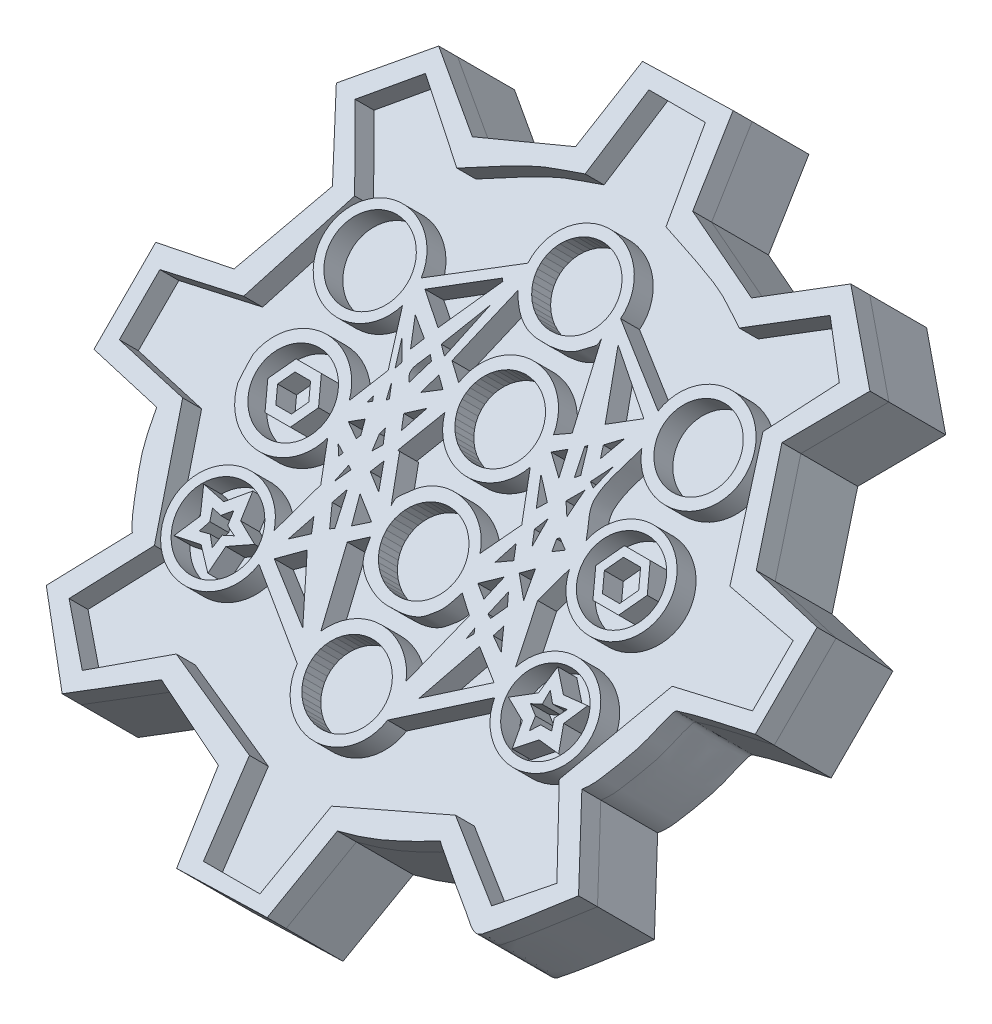
SolidWorks part; units mm, degrees
ref_plane "Front Plane" through (0, 0, 0) normal (0, 0, 1) x (1, 0, 0)
ref_plane "Top Plane" through (0, 0, 0) normal (0, 1, 0) x (1, 0, 0)
ref_plane "Right Plane" through (0, 0, 0) normal (1, 0, 0) x (0, 0, -1)
ref_plane "Plane2" through (0, -6.35, 0) normal (0, 1, 0) x (1, 0, 0)
sketch "Sketch2" plane through (0, -6.35, 0) normal (0, 1, 0) x (1, 0, 0)
  circle A0 centre (0, 0) radius 6.0325
  dimension "D1" = 12.065
ref_axis "Axis1" through (-6.2865, 0, 0) along (1, 0, 0)
ref_plane "Plane1" through (0, 0, 0) normal (0, 0.7071, 0.7071) x (1, 0, 0)
sketch "Sketch3" plane through (0, 0, 0) normal (0, 0.7071, 0.7071) x (1, 0, 0)
  line L0 (0, 0) -> (-25.4, 0) construction
  line L1 (-6.2865, 0) -> (6.2865, 0) construction
  line L2 (-25.4, -38.1) -> (-25.4, 38.1) construction
  circle A0 centre (0, 0) radius 12.7
  point P13 (-25.4, 0)
  point P15 (-20.32, 7.62)
  point P16 (-20.32, -7.62)
  point P17 (-20.32, -22.86)
  dimension "D1" = 25.4
  dimension "D4" = 25.4
  dimension "D5" = 76.2
extrude "Boss-Extrude1" add sketch "Sketch3" along normal blind 4.7625
extrude "Boss-Extrude2" add sketch "Sketch2" along normal up to surface and the other way blind 3.175 up to face at (0, -8.9803, 8.9803)
sketch "Sketch5" plane through (0, 3.3676, 3.3676) normal (0, 0.7071, 0.7071) x (1, 0, 0)
  line L0 (2.1384, 9.1764) -> (2.1514, 9.4647)
  line L1 (2.1514, 9.4647) -> (2.125, 9.7523)
  line L2 (2.125, 9.7523) -> (2.0598, 10.0341)
  line L3 (2.0598, 10.0341) -> (1.9568, 10.3051)
  line L4 (1.9568, 10.3051) -> (1.818, 10.5603)
  line L5 (1.818, 10.5603) -> (1.6457, 10.7953)
  line L6 (1.6457, 10.7953) -> (1.4431, 11.0059)
  line L7 (1.4431, 11.0059) -> (1.2138, 11.1882)
  line L8 (1.2138, 11.1882) -> (0.9619, 11.3391)
  line L9 (0.9619, 11.3391) -> (0.6918, 11.4559)
  line L10 (0.6918, 11.4559) -> (0.4085, 11.5365)
  line L11 (0.4085, 11.5365) -> (0.1168, 11.5794)
  line L12 (0.1168, 11.5794) -> (-0.1778, 11.5838)
  line L13 (-0.1778, 11.5838) -> (-0.4703, 11.5498)
  line L14 (-0.4703, 11.5498) -> (-0.7553, 11.4779)
  line L15 (-0.7553, 11.4779) -> (-1.0279, 11.3693)
  line L16 (-1.0279, 11.3693) -> (-1.283, 11.2261)
  line L17 (-1.283, 11.2261) -> (-1.5162, 11.0507)
  line L18 (-1.5162, 11.0507) -> (-1.7233, 10.8463)
  line L19 (-1.7233, 10.8463) -> (-1.9007, 10.6166)
  line L20 (-1.9007, 10.6166) -> (-2.045, 10.3657)
  line L21 (-2.045, 10.3657) -> (-2.1539, 10.098)
  line L22 (-2.1539, 10.098) -> (-2.2253, 9.8183)
  line L23 (-2.2253, 9.8183) -> (-2.2579, 9.5315)
  line L24 (-2.2579, 9.5315) -> (-2.2512, 9.243)
  line L25 (-2.2512, 9.243) -> (-2.2053, 8.9576)
  line L26 (-2.2053, 8.9576) -> (-2.121, 8.6806)
  line L27 (-2.121, 8.6806) -> (-1.9998, 8.417)
  line L28 (-1.9998, 8.417) -> (-1.8439, 8.1713)
  line L29 (-1.8439, 8.1713) -> (-1.6561, 7.948)
  line L30 (-1.6561, 7.948) -> (-1.4396, 7.7511)
  line L31 (-1.4396, 7.7511) -> (-1.1985, 7.5841)
  line L32 (-1.1985, 7.5841) -> (-0.9369, 7.45)
  line L33 (-0.9369, 7.45) -> (-0.6596, 7.3511)
  line L34 (-0.6596, 7.3511) -> (-0.3714, 7.2892)
  line L35 (-0.3714, 7.2892) -> (-0.0776, 7.2655)
  line L36 (-0.0776, 7.2655) -> (0.2166, 7.2803)
  line L37 (0.2166, 7.2803) -> (0.506, 7.3334)
  line L38 (0.506, 7.3334) -> (0.7854, 7.4239)
  line L39 (0.7854, 7.4239) -> (1.0498, 7.55)
  line L40 (1.0498, 7.55) -> (1.2946, 7.7097)
  line L41 (1.2946, 7.7097) -> (1.5152, 7.9)
  line L42 (1.5152, 7.9) -> (1.7079, 8.1175)
  line L43 (1.7079, 8.1175) -> (1.8691, 8.3584)
  line L44 (1.8691, 8.3584) -> (1.996, 8.6183)
  line L45 (1.996, 8.6183) -> (2.0863, 8.8926)
  line L46 (2.0863, 8.8926) -> (2.1384, 9.1764)
  line L47 (2.1553, 2.9225) -> (2.146, 3.2114)
  line L48 (2.146, 3.2114) -> (2.0975, 3.4967)
  line L49 (2.0975, 3.4967) -> (2.0105, 3.7731)
  line L50 (2.0105, 3.7731) -> (1.8868, 4.0357)
  line L51 (1.8868, 4.0357) -> (1.7284, 4.2799)
  line L52 (1.7284, 4.2799) -> (1.5383, 4.5013)
  line L53 (1.5383, 4.5013) -> (1.3198, 4.696)
  line L54 (1.3198, 4.696) -> (1.0768, 4.8604)
  line L55 (1.0768, 4.8604) -> (0.8136, 4.9916)
  line L56 (0.8136, 4.9916) -> (0.535, 5.0874)
  line L57 (0.535, 5.0874) -> (0.2459, 5.1459)
  line L58 (0.2459, 5.1459) -> (-0.0486, 5.1662)
  line L59 (-0.0486, 5.1662) -> (-0.3431, 5.1478)
  line L60 (-0.3431, 5.1478) -> (-0.6324, 5.0912)
  line L61 (-0.6324, 5.0912) -> (-0.9114, 4.9973)
  line L62 (-0.9114, 4.9973) -> (-1.1751, 4.8677)
  line L63 (-1.1751, 4.8677) -> (-1.4187, 4.7049)
  line L64 (-1.4187, 4.7049) -> (-1.638, 4.5117)
  line L65 (-1.638, 4.5117) -> (-1.8289, 4.2915)
  line L66 (-1.8289, 4.2915) -> (-1.9882, 4.0484)
  line L67 (-1.9882, 4.0484) -> (-2.1129, 3.7865)
  line L68 (-2.1129, 3.7865) -> (-2.2009, 3.5107)
  line L69 (-2.2009, 3.5107) -> (-2.2505, 3.2258)
  line L70 (-2.2505, 3.2258) -> (-2.2609, 2.9369)
  line L71 (-2.2609, 2.9369) -> (-2.2319, 2.6491)
  line L72 (-2.2319, 2.6491) -> (-2.164, 2.3677)
  line L73 (-2.164, 2.3677) -> (-2.0585, 2.0975)
  line L74 (-2.0585, 2.0975) -> (-1.9171, 1.8436)
  line L75 (-1.9171, 1.8436) -> (-1.7425, 1.6102)
  line L76 (-1.7425, 1.6102) -> (-1.5377, 1.4017)
  line L77 (-1.5377, 1.4017) -> (-1.3064, 1.2218)
  line L78 (-1.3064, 1.2218) -> (-1.0527, 1.0737)
  line L79 (-1.0527, 1.0737) -> (-0.7812, 0.9599)
  line L80 (-0.7812, 0.9599) -> (-0.4967, 0.8826)
  line L81 (-0.4967, 0.8826) -> (-0.2043, 0.8431)
  line L82 (-0.2043, 0.8431) -> (0.0908, 0.8421)
  line L83 (0.0908, 0.8421) -> (0.3834, 0.8797)
  line L84 (0.3834, 0.8797) -> (0.6682, 0.9552)
  line L85 (0.6682, 0.9552) -> (0.9401, 1.0671)
  line L86 (0.9401, 1.0671) -> (1.1944, 1.2137)
  line L87 (1.1944, 1.2137) -> (1.4263, 1.3921)
  line L88 (1.4263, 1.3921) -> (1.6319, 1.5992)
  line L89 (1.6319, 1.5992) -> (1.8074, 1.8314)
  line L90 (1.8074, 1.8314) -> (1.9497, 2.0845)
  line L91 (1.9497, 2.0845) -> (2.0563, 2.3539)
  line L92 (2.0563, 2.3539) -> (2.1252, 2.6349)
  line L93 (2.1252, 2.6349) -> (2.1553, 2.9225)
  line L94 (2.1447, -3.5357) -> (2.1432, -3.2468)
  line L95 (2.1432, -3.2468) -> (2.1025, -2.9605)
  line L96 (2.1025, -2.9605) -> (2.0232, -2.682)
  line L97 (2.0232, -2.682) -> (1.9066, -2.4162)
  line L98 (1.9066, -2.4162) -> (1.755, -2.1679)
  line L99 (1.755, -2.1679) -> (1.571, -1.9415)
  line L100 (1.571, -1.9415) -> (1.3579, -1.7411)
  line L101 (1.3579, -1.7411) -> (1.1195, -1.5702)
  line L102 (1.1195, -1.5702) -> (0.8601, -1.4319)
  line L103 (0.8601, -1.4319) -> (0.5842, -1.3286)
  line L104 (0.5842, -1.3286) -> (0.2968, -1.2622)
  line L105 (0.2968, -1.2622) -> (0.003, -1.2339)
  line L106 (0.003, -1.2339) -> (-0.2918, -1.2442)
  line L107 (-0.2918, -1.2442) -> (-0.5826, -1.2929)
  line L108 (-0.5826, -1.2929) -> (-0.864, -1.3791)
  line L109 (-0.864, -1.3791) -> (-1.1311, -1.5013)
  line L110 (-1.1311, -1.5013) -> (-1.379, -1.6573)
  line L111 (-1.379, -1.6573) -> (-1.6034, -1.8443)
  line L112 (-1.6034, -1.8443) -> (-1.8003, -2.059)
  line L113 (-1.8003, -2.059) -> (-1.9662, -2.2976)
  line L114 (-1.9662, -2.2976) -> (-2.098, -2.5558)
  line L115 (-2.098, -2.5558) -> (-2.1934, -2.8289)
  line L116 (-2.1934, -2.8289) -> (-2.2508, -3.1122)
  line L117 (-2.2508, -3.1122) -> (-2.2691, -3.4006)
  line L118 (-2.2691, -3.4006) -> (-2.248, -3.6888)
  line L119 (-2.248, -3.6888) -> (-2.1878, -3.9719)
  line L120 (-2.1878, -3.9719) -> (-2.0896, -4.2446)
  line L121 (-2.0896, -4.2446) -> (-1.9553, -4.5022)
  line L122 (-1.9553, -4.5022) -> (-1.7871, -4.7401)
  line L123 (-1.7871, -4.7401) -> (-1.5881, -4.954)
  line L124 (-1.5881, -4.954) -> (-1.3618, -5.1401)
  line L125 (-1.3618, -5.1401) -> (-1.1123, -5.295)
  line L126 (-1.1123, -5.295) -> (-0.8441, -5.4161)
  line L127 (-0.8441, -5.4161) -> (-0.5618, -5.5011)
  line L128 (-0.5618, -5.5011) -> (-0.2706, -5.5485)
  line L129 (-0.2706, -5.5485) -> (0.0244, -5.5576)
  line L130 (0.0244, -5.5576) -> (0.3179, -5.528)
  line L131 (0.3179, -5.528) -> (0.6046, -5.4604)
  line L132 (0.6046, -5.4604) -> (0.8794, -5.356)
  line L133 (0.8794, -5.356) -> (1.1375, -5.2166)
  line L134 (1.1375, -5.2166) -> (1.3742, -5.0447)
  line L135 (1.3742, -5.0447) -> (1.5854, -4.8434)
  line L136 (1.5854, -4.8434) -> (1.7671, -4.6162)
  line L137 (1.7671, -4.6162) -> (1.9163, -4.3673)
  line L138 (1.9163, -4.3673) -> (2.0302, -4.101)
  line L139 (2.0302, -4.101) -> (2.1067, -3.8222)
  line L140 (2.1067, -3.8222) -> (2.1447, -3.5357)
  line L141 (2.1098, -10.2575) -> (2.1477, -9.9761)
  line L142 (2.1477, -9.9761) -> (2.1479, -9.692)
  line L143 (2.1479, -9.692) -> (2.1103, -9.41)
  line L144 (2.1103, -9.41) -> (2.0357, -9.135)
  line L145 (2.0357, -9.135) -> (1.9252, -8.8716)
  line L146 (1.9252, -8.8716) -> (1.7807, -8.6245)
  line L147 (1.7807, -8.6245) -> (1.6048, -8.3977)
  line L148 (1.6048, -8.3977) -> (1.4005, -8.1951)
  line L149 (1.4005, -8.1951) -> (1.1711, -8.0204)
  line L150 (1.1711, -8.0204) -> (0.9208, -7.8763)
  line L151 (0.9208, -7.8763) -> (0.6537, -7.7655)
  line L152 (0.6537, -7.7655) -> (0.3744, -7.6897)
  line L153 (0.3744, -7.6897) -> (0.0877, -7.6504)
  line L154 (0.0877, -7.6504) -> (-0.2014, -7.6481)
  line L155 (-0.2014, -7.6481) -> (-0.4882, -7.6829)
  line L156 (-0.4882, -7.6829) -> (-0.7675, -7.7542)
  line L157 (-0.7675, -7.7542) -> (-1.0348, -7.8608)
  line L158 (-1.0348, -7.8608) -> (-1.2853, -8.0008)
  line L159 (-1.2853, -8.0008) -> (-1.5148, -8.172)
  line L160 (-1.5148, -8.172) -> (-1.7194, -8.3712)
  line L161 (-1.7194, -8.3712) -> (-1.8956, -8.5952)
  line L162 (-1.8956, -8.5952) -> (-2.0403, -8.8401)
  line L163 (-2.0403, -8.8401) -> (-2.1511, -9.1017)
  line L164 (-2.1511, -9.1017) -> (-2.2262, -9.3755)
  line L165 (-2.2262, -9.3755) -> (-2.2641, -9.6569)
  line L166 (-2.2641, -9.6569) -> (-2.2642, -9.941)
  line L167 (-2.2642, -9.941) -> (-2.2267, -10.223)
  line L168 (-2.2267, -10.223) -> (-2.152, -10.498)
  line L169 (-2.152, -10.498) -> (-2.0415, -10.7613)
  line L170 (-2.0415, -10.7613) -> (-1.897, -11.0085)
  line L171 (-1.897, -11.0085) -> (-1.7211, -11.2353)
  line L172 (-1.7211, -11.2353) -> (-1.5168, -11.4378)
  line L173 (-1.5168, -11.4378) -> (-1.2875, -11.6126)
  line L174 (-1.2875, -11.6126) -> (-1.0371, -11.7567)
  line L175 (-1.0371, -11.7567) -> (-0.77, -11.8675)
  line L176 (-0.77, -11.8675) -> (-0.4907, -11.9433)
  line L177 (-0.4907, -11.9433) -> (-0.2041, -11.9826)
  line L178 (-0.2041, -11.9826) -> (0.0851, -11.9849)
  line L179 (0.0851, -11.9849) -> (0.3718, -11.9501)
  line L180 (0.3718, -11.9501) -> (0.6512, -11.8788)
  line L181 (0.6512, -11.8788) -> (0.9184, -11.7722)
  line L182 (0.9184, -11.7722) -> (1.169, -11.6321)
  line L183 (1.169, -11.6321) -> (1.3985, -11.461)
  line L184 (1.3985, -11.461) -> (1.6031, -11.2618)
  line L185 (1.6031, -11.2618) -> (1.7793, -11.0378)
  line L186 (1.7793, -11.0378) -> (1.924, -10.7929)
  line L187 (1.924, -10.7929) -> (2.0348, -10.5313)
  line L188 (2.0348, -10.5313) -> (2.1098, -10.2575)
  line L189 (11.1815, -5.5544) -> (9.8248, -5.6673)
  line L190 (9.1225, -5.7799) -> (9.1225, -6.4565)
  line L191 (9.1225, -6.4565) -> (8.5826, -6.6798)
  line L192 (8.5826, -6.6798) -> (9.1225, -7.0175)
  line L193 (9.1225, -7.0175) -> (9.2346, -7.6897)
  line L194 (9.2346, -7.6897) -> (9.5792, -7.2361)
  line L195 (9.5792, -7.2361) -> (10.233, -7.2361)
  line L196 (10.233, -7.2361) -> (10.011, -6.6996)
  line L197 (10.011, -6.6996) -> (10.3747, -6.1182)
  line L198 (10.3747, -6.1182) -> (9.5792, -6.227)
  line L199 (9.5792, -6.227) -> (9.1225, -5.7799)
  line L200 (10.5709, -6.6996) -> (11.1815, -5.5544)
  line L201 (11.1233, -7.9115) -> (10.5709, -6.6996)
  line L202 (9.9061, -7.8107) -> (11.1233, -7.9115)
  line L203 (8.9329, -8.7049) -> (9.9061, -7.8107)
  line L204 (8.6664, -7.4675) -> (8.9329, -8.7049)
  line L205 (7.4397, -6.9096) -> (8.6664, -7.4675)
  line L206 (8.6664, -6.1182) -> (7.4397, -6.9096)
  line L207 (8.8526, -4.7674) -> (8.6664, -6.1182)
  line L208 (9.8248, -5.6673) -> (8.8526, -4.7674)
  line L209 (7.9446, -0.3005) -> (8.7074, -1.6217)
  line L210 (10.4872, -0.3005) -> (9.9787, 0.5803)
  line L211 (9.9787, 0.5803) -> (8.9617, 0.5803)
  line L212 (8.9617, 0.5803) -> (8.4532, -0.3005)
  line L213 (8.4532, -0.3005) -> (8.9617, -1.1812)
  line L214 (8.9617, -1.1812) -> (9.9787, -1.1812)
  line L215 (9.9787, -1.1812) -> (10.4872, -0.3005)
  line L216 (8.7074, 1.0207) -> (7.9446, -0.3005)
  line L217 (10.233, 1.0207) -> (8.7074, 1.0207)
  line L218 (10.9958, -0.3005) -> (10.233, 1.0207)
  line L219 (10.233, -1.6217) -> (10.9958, -0.3005)
  line L220 (8.7074, -1.6217) -> (10.233, -1.6217)
  line L221 (-11.4271, -0.3799) -> (-10.6764, -1.6802)
  line L222 (-9.0014, -0.3799) -> (-9.4635, 0.4205)
  line L223 (-9.4635, 0.4205) -> (-10.3877, 0.4205)
  line L224 (-10.3877, 0.4205) -> (-10.8498, -0.3799)
  line L225 (-10.8498, -0.3799) -> (-10.3877, -1.1803)
  line L226 (-10.3877, -1.1803) -> (-9.4635, -1.1803)
  line L227 (-9.4635, -1.1803) -> (-9.0014, -0.3799)
  line L228 (-10.6764, 0.9204) -> (-11.4271, -0.3799)
  line L229 (-9.1749, 0.9204) -> (-10.6764, 0.9204)
  line L230 (-8.4241, -0.3799) -> (-9.1749, 0.9204)
  line L231 (-9.1749, -1.6802) -> (-8.4241, -0.3799)
  line L232 (-10.6764, -1.6802) -> (-9.1749, -1.6802)
  line L233 (-9.9942, -7.2361) -> (-10.5615, -7.3583)
  line L234 (-11.5651, -5.5544) -> (-10.2232, -5.7799)
  line L235 (-10.2232, -5.7799) -> (-9.2055, -4.7798)
  line L236 (-9.2055, -4.7798) -> (-8.9824, -6.1183)
  line L237 (-8.9824, -6.1183) -> (-7.7542, -6.6768)
  line L238 (-7.7542, -6.6768) -> (-8.9824, -7.3583)
  line L239 (-8.9824, -7.3583) -> (-9.0939, -8.7049)
  line L240 (-9.0939, -8.7049) -> (-10.1253, -7.8107)
  line L241 (-10.1253, -7.8107) -> (-11.5651, -8.0507)
  line L242 (-11.5651, -8.0507) -> (-10.8942, -6.7924)
  line L243 (-10.8942, -6.7924) -> (-11.5651, -5.5544)
  line L244 (-9.5485, -7.6897) -> (-9.9942, -7.2361)
  line L245 (-9.4371, -7.0269) -> (-9.5485, -7.6897)
  line L246 (-8.8749, -6.7924) -> (-9.4371, -7.0269)
  line L247 (-9.4371, -6.5611) -> (-8.8749, -6.7924)
  line L248 (-9.5485, -5.8929) -> (-9.4371, -6.5611)
  line L249 (-10.0073, -6.3437) -> (-9.5485, -5.8929)
  line L250 (-10.5615, -6.2297) -> (-10.0073, -6.3437)
  line L251 (-10.3287, -6.7924) -> (-10.5615, -6.2297)
  line L252 (-10.5615, -7.3583) -> (-10.3287, -6.7924)
  line L253 (2.5066, 1.9018) -> (3.6134, -0.3799)
  line L254 (3.6134, -4.7674) -> (2.4884, -8.4799)
  line L255 (-3.6991, 4.1201) -> (-2.8364, 3.4604)
  line L256 (6.2009, 3.6701) -> (5.555, 2.634)
  line L257 (-6.5116, 3.8951) -> (-6.033, 2.6576)
  line L258 (5.5259, 2.2076) -> (4.9634, 1.4201)
  line L259 (-3.4238, 6.9255) -> (-4.5991, 4.493)
  line L260 (-3.4741, 8.0576) -> (-5.1616, 5.0201)
  line L261 (3.2759, 8.1701) -> (6.3134, 6.0326)
  line L262 (-6.5116, 5.0201) -> (-5.4991, 4.3451)
  line L263 (4.9634, 2.6576) -> (4.7384, 2.4326)
  line L264 (-3.9241, 3.3326) -> (-3.3616, 2.8826)
  line L265 (3.7259, 3.3326) -> (4.0634, 2.0951)
  line L266 (-5.8366, 2.0951) -> (-5.4991, 1.4201)
  line L267 (-3.5866, 1.8701) -> (-4.1491, 0.5201)
  line L268 (3.1634, 1.8701) -> (4.1759, 0.9701)
  line L269 (-6.2866, 1.1951) -> (-6.1741, 0.9701)
  line L270 (4.6259, 0.4076) -> (4.6259, -0.9424)
  line L271 (-4.5991, -0.3799) -> (-4.9366, -0.8299)
  line L272 (-5.8366, -0.4924) -> (-5.9491, -0.7174)
  line L273 (6.2009, -0.3799) -> (5.6384, -0.7174)
  line L274 (-4.1491, -0.9424) -> (-3.5866, -2.1799)
  line L275 (3.8384, -1.1674) -> (4.1759, -1.8424)
  line L276 (-6.6241, -1.2799) -> (-6.1741, -1.5049)
  line L277 (-5.6116, -1.8424) -> (-5.3866, -1.9549)
  line L278 (-4.3741, -2.6299) -> (-3.1366, -3.4174)
  line L279 (4.1759, -2.6299) -> (3.8384, -3.8674)
  line L280 (-4.5991, -4.4299) -> (-4.8241, -4.5424)
  line L281 (5.0759, -3.6424) -> (4.6259, -4.4299)
  line L282 (-5.8366, -4.4299) -> (-5.4991, -5.1049)
  line L283 (5.4134, -4.4299) -> (5.9759, -5.4424)
  line L284 (4.8509, -5.6674) -> (6.4259, -6.6799)
  line L285 (-5.2741, -5.7799) -> (-3.4741, -8.7049)
  line L286 (4.7384, -2.1799) -> (5.347, -1.6823)
  line L287 (-4.8241, 3.8951) -> (-4.5991, 3.6701)
  line L288 (2.7134, -4.0924) -> (3.6134, -4.7674)
  line L289 (-3.6991, -4.6549) -> (-2.7991, -3.9799)
  line L290 (-2.585, -8.443) -> (-3.6991, -4.6549)
  line L291 (3.5009, 4.0076) -> (2.7134, 3.5576)
  line L292 (2.3759, 8.0576) -> (3.5009, 4.0076)
  line L293 (-3.6991, 4.1201) -> (-2.5741, 8.0576)
  line L294 (5.555, 2.634) -> (5.8506, 2.4498)
  line L295 (5.8506, 2.4498) -> (6.2009, 3.6701)
  line L296 (-5.8854, 3.002) -> (-6.5116, 3.8951)
  line L297 (4.9634, 1.4201) -> (5.4134, 0.8576)
  line L298 (5.4134, 0.8576) -> (5.5259, 2.2076)
  line L299 (-4.5991, 4.493) -> (-4.1491, 4.1201)
  line L300 (-4.1491, 4.1201) -> (-3.4238, 6.9255)
  line L301 (-3.5866, 8.1701) -> (-3.4741, 8.0576)
  line L302 (-6.7366, 6.1451) -> (-3.5866, 8.1701)
  line L303 (-5.1616, 5.0201) -> (-6.7366, 6.1451)
  line L304 (4.7384, 5.0201) -> (3.2759, 8.1701)
  line L305 (6.3134, 6.0326) -> (4.7384, 5.0201)
  line L306 (-5.8366, 3.6701) -> (-6.5116, 5.0201)
  line L307 (-5.4991, 4.3451) -> (-5.8366, 3.6701)
  line L308 (5.1884, 4.2326) -> (5.9759, 4.9076)
  line L309 (5.4134, 3.6701) -> (5.1884, 4.2326)
  line L310 (4.5134, 3.8951) -> (4.9634, 2.6576)
  line L311 (4.4009, 3.7826) -> (4.5134, 3.8951)
  line L312 (4.7384, 2.4326) -> (4.4009, 3.7826)
  line L313 (-4.2616, 2.3201) -> (-3.9241, 3.3326)
  line L314 (-3.3616, 2.8826) -> (-4.2616, 2.3201)
  line L315 (3.0509, 2.8826) -> (3.7259, 3.3326)
  line L316 (4.0634, 2.0951) -> (3.0509, 2.8826)
  line L317 (-5.6116, 1.3076) -> (-5.8366, 2.0951)
  line L318 (-5.4991, 1.4201) -> (-5.6116, 1.3076)
  line L319 (-4.4866, 1.1951) -> (-3.5866, 1.8701)
  line L320 (-4.1491, 0.5201) -> (-4.4866, 1.1951)
  line L321 (3.8384, 0.5201) -> (3.1634, 1.8701)
  line L322 (4.1759, 0.9701) -> (3.8384, 0.5201)
  line L323 (-6.3991, 0.8576) -> (-6.2866, 1.1951)
  line L324 (-6.1741, 0.9701) -> (-6.3991, 0.8576)
  line L325 (4.2884, -0.2674) -> (4.6259, 0.4076)
  line L326 (4.6259, -0.9424) -> (4.2884, -0.2674)
  line L327 (-4.9366, 0.2951) -> (-4.5991, -0.3799)
  line L328 (-5.0491, -0.0424) -> (-4.9366, 0.2951)
  line L329 (-4.9366, -0.8299) -> (-5.0491, -0.0424)
  line L330 (-6.0616, 0.1826) -> (-5.8366, -0.4924)
  line L331 (-6.7366, -0.2674) -> (-6.0616, 0.1826)
  line L332 (-5.9491, -0.7174) -> (-6.7366, -0.2674)
  line L333 (5.6384, -0.0424) -> (6.2009, -0.3799)
  line L334 (5.5259, -0.1549) -> (5.6384, -0.0424)
  line L335 (5.6384, -0.7174) -> (5.5259, -0.1549)
  line L336 (-4.4866, -1.6174) -> (-4.1491, -0.9424)
  line L337 (-3.5866, -2.1799) -> (-4.4866, -1.6174)
  line L338 (3.3884, -2.2924) -> (3.8384, -1.1674)
  line L339 (4.1759, -1.8424) -> (3.3884, -2.2924)
  line L340 (-6.2866, -1.7299) -> (-6.6241, -1.2799)
  line L341 (-6.1741, -1.5049) -> (-6.2866, -1.7299)
  line L342 (-5.8366, -2.7424) -> (-5.6116, -1.8424)
  line L343 (-5.3866, -1.9549) -> (-5.8366, -2.7424)
  line L344 (-3.9241, -3.9799) -> (-4.3741, -2.6299)
  line L345 (-3.1366, -3.4174) -> (-3.9241, -3.9799)
  line L346 (3.1634, -3.4174) -> (4.1759, -2.6299)
  line L347 (3.8384, -3.8674) -> (3.1634, -3.4174)
  line L348 (-5.0491, -2.7424) -> (-4.5991, -4.4299)
  line L349 (-5.3866, -3.5299) -> (-5.0491, -2.7424)
  line L350 (-4.8241, -4.5424) -> (-5.3866, -3.5299)
  line L351 (4.7384, -3.0799) -> (5.0759, -3.6424)
  line L352 (4.4009, -4.3174) -> (4.7384, -3.0799)
  line L353 (4.6259, -4.4299) -> (4.4009, -4.3174)
  line L354 (-6.3991, -5.7799) -> (-5.8366, -4.4299)
  line L355 (-5.4991, -5.1049) -> (-6.3991, -5.7799)
  line L356 (5.1884, -4.9924) -> (5.4134, -4.4299)
  line L357 (5.9759, -5.4424) -> (5.1884, -4.9924)
  line L358 (4.0634, -5.6674) -> (4.1759, -5.1049)
  line L359 (4.2884, -5.3299) -> (4.0634, -5.6674)
  line L360 (3.5009, -8.8174) -> (4.8509, -5.6674)
  line L361 (6.4259, -6.6799) -> (3.5009, -8.8174)
  line L362 (-6.5116, -6.7924) -> (-5.2741, -5.7799)
  line L363 (-3.4741, -8.7049) -> (-6.5116, -6.7924)
  line L364 (5.6384, -3.0799) -> (4.7384, -2.1799)
  line L365 (5.347, -1.6823) -> (5.6384, -3.0799)
  line L366 (6.9884, -5.6673) -> (6.2574, -2.7867)
  line L367 (6.843, -7.2114) -> (2.6619, -10.2672)
  line L368 (-2.7991, -10.1154) -> (-7.0549, -7.3059)
  line L369 (-7.2401, -5.7799) -> (-6.3459, -3.1325)
  line L370 (-6.3459, -3.1325) -> (-7.2401, -1.2799)
  line L371 (-7.2401, 0.5201) -> (-6.2866, 2.4327)
  line L372 (-7.3159, 5.094) -> (-6.2866, 2.4327)
  line L373 (-7.1866, 6.4748) -> (-2.827, 9.2491)
  line L374 (2.7134, 9.1764) -> (6.751, 6.6092)
  line L375 (-4.5991, 3.6701) -> (-5.0491, 2.4326)
  line L376 (-3.8116, -0.2674) -> (-2.6866, 2.0951)
  line L377 (-3.6991, -0.2674) -> (-3.8116, -0.2674)
  line L378 (-2.6866, -2.4049) -> (-3.6991, -0.2674)
  line L379 (3.6134, -0.3799) -> (2.4884, -2.2924)
  line L380 (5.9759, 4.9076) -> (5.4134, 3.6701)
  line L381 (4.1759, -5.1049) -> (4.2884, -5.3299)
  line L382 (6.2574, -2.7867) -> (6.868, -0.979)
  line L383 (-6.033, 2.6576) -> (-5.8854, 3.002)
  line L384 (-12.2491, 8.0576) -> (-14.6116, 2.0951)
  line L385 (-19.014, 1.3076) -> (-14.6116, 2.0951)
  line L386 (-12.1792, -8.8174) -> (-14.7114, -2.8713)
  line L387 (-12.1792, -14.8613) -> (-14.6116, -12.5299)
  line L388 (-14.7114, 11.5722) -> (-12.2491, 8.0576)
  line L389 (-8.4241, -12.2962) -> (-2.5741, -14.4424)
  line L390 (-1.8991, -19.2478) -> (-2.5741, -14.4424)
  line L391 (-1.8991, -19.2478) -> (1.4449, -19.2478)
  line L392 (1.4449, -19.2478) -> (2.3759, -14.5643)
  line L393 (-19.014, -2.0891) -> (-14.7114, -2.8713)
  line L394 (8.1134, -12.2962) -> (12.0509, -14.8312)
  line L395 (14.3676, -12.6424) -> (12.0509, -14.8312)
  line L396 (11.804, -8.8174) -> (14.3676, -12.6424)
  line L397 (-12.1792, -14.8613) -> (-8.4241, -12.2962)
  line L398 (18.6402, -2.2924) -> (14.4368, -3.0799)
  line L399 (18.6402, 1.1109) -> (18.6402, -2.2924)
  line L400 (14.4368, 1.7576) -> (18.6402, 1.1109)
  line L401 (-19.014, -2.0891) -> (-19.014, 1.3076)
  line L402 (14.0759, 11.4326) -> (11.9384, 8.0576)
  line L403 (11.9384, 13.6826) -> (14.0759, 11.4326)
  line L404 (-14.6116, -12.5299) -> (-12.1792, -8.8174)
  line L405 (1.4449, 18.0701) -> (2.3759, 13.4576)
  line L406 (-1.8991, 18.0701) -> (1.4449, 18.0701)
  line L407 (-2.5741, 13.6826) -> (-1.8991, 18.0701)
  line L408 (-12.2491, 13.9853) -> (-8.4241, 11.2076)
  line L409 (2.3759, -19.9549) -> (3.2759, -15.3424)
  line L410 (2.3759, -19.9549) -> (-2.9116, -20.0674)
  line L411 (-3.6991, -15.4549) -> (-2.9116, -20.0674)
  line L412 (14.4368, -3.0799) -> (11.804, -8.8174)
  line L413 (-12.4741, -16.1299) -> (-8.4241, -13.5424)
  line L414 (-15.9616, -12.5299) -> (-12.4741, -16.1299)
  line L415 (-13.4866, -8.8174) -> (-15.9616, -12.5299)
  line L416 (-19.8991, -2.9674) -> (-15.6241, -3.7549)
  line L417 (-19.8991, -2.9674) -> (-19.8991, 2.2076)
  line L418 (-15.7366, 2.8826) -> (-19.8991, 2.2076)
  line L419 (-13.4866, 7.9451) -> (-15.7366, 2.8826)
  line L420 (-15.9616, 11.7701) -> (-13.4866, 7.9451)
  line L421 (-12.3616, 15.2576) -> (-15.9616, 11.7701)
  line L422 (-8.5366, 12.6701) -> (-12.3616, 15.2576)
  line L423 (-3.6991, 14.4701) -> (-8.5366, 12.6701)
  line L424 (-2.9116, 18.9701) -> (-3.6991, 14.4701)
  line L425 (2.3759, -14.5643) -> (8.1134, -12.2962)
  line L426 (3.1634, 14.5826) -> (2.3759, 19.0826)
  line L427 (8.0009, 12.6701) -> (3.1634, 14.5826)
  line L428 (12.0509, 15.2576) -> (8.0009, 12.6701)
  line L429 (15.6509, 11.7701) -> (12.0509, 15.2576)
  line L430 (13.0634, 8.0576) -> (15.6509, 11.7701)
  line L431 (15.2009, 2.8826) -> (13.0634, 8.0576)
  line L432 (19.3634, 2.0951) -> (15.2009, 2.8826)
  line L433 (19.3634, 2.0951) -> (19.3634, -3.0799)
  line L434 (15.6509, -12.6424) -> (13.0634, -8.7049)
  line L435 (8.2259, 11.3201) -> (11.9384, 13.6826)
  line L436 (-14.7114, 11.5722) -> (-12.2491, 13.9853)
  line L437 (11.9384, 8.0576) -> (14.4368, 1.7576)
  line L438 (-8.4241, -13.5424) -> (-3.6991, -15.4549)
  line L439 (-2.9116, 18.9701) -> (2.3759, 19.0826)
  circle A0 centre (9.4909, 6.1241) radius 2.1625
  circle A1 centre (-9.9256, -0.3799) radius 2.1919
  circle A2 centre (9.4702, -0.3005) radius 2.185
  circle A3 centre (-9.7958, -6.8643) radius 2.2672
  circle A4 centre (-9.9039, 6.0327) radius 2.2368
  circle A5 centre (9.4702, -6.6798) radius 2.1642
  arc A6 (2.4884, -8.4799) -> (-2.585, -8.443) centre (-0.0582, -9.8165) ccw
  arc A7 (2.7134, 3.5576) -> (-2.8364, 3.4604) centre (-0.0527, 3.002) ccw
  arc A8 (6.843, -7.2114) -> (6.9884, -5.6673) centre (9.4702, -6.6798) ccw
  arc A9 (-2.7991, -10.1154) -> (2.6619, -10.2672) centre (-0.0582, -9.8165) ccw
  arc A10 (-7.2401, -5.7799) -> (-7.0549, -7.3059) centre (-9.7958, -6.8643) ccw
  arc A11 (-7.2401, 0.5201) -> (-7.2401, -1.2799) centre (-9.9256, -0.3799) ccw
  arc A12 (-7.1866, 6.4748) -> (-7.3159, 5.094) centre (-9.9039, 6.0327) ccw
  arc A13 (2.7134, 9.1764) -> (-2.827, 9.2491) centre (-0.054, 9.426) ccw
  arc A14 (6.9884, 4.9077) -> (6.751, 6.6092) centre (9.4909, 6.1241) ccw
  arc A15 (6.868, -0.979) -> (6.8759, 0.4077) centre (9.4702, -0.3005) ccw
  arc A16 (-2.6866, 2.0951) -> (2.5066, 1.9018) centre (-0.0527, 3.002) ccw
  spline S0 degree 3 poles (-2.7991, -3.9799) (-2.7241, -4.2799) (-2.7021, -4.5984) (-2.5741, -4.8799) (-2.2447, -5.6045) (-1.0499, -6.1174) (-0.3241, -6.1174) (0.2812, -6.1174) (1.1746, -6.141) (1.7009, -5.6674) (2.4016, -5.0368) (2.372, -4.889) (2.7134, -4.0924) knots 0 0 0 0 1 1 1 2 2 2 3 3 3 4 4 4 4
  spline S1 degree 3 poles (-2.5741, 8.0576) (-2.1046, 7.3533) (-1.4724, 6.7846) (-0.5491, 6.7076) (0.0361, 6.6588) (1.1397, 6.6526) (1.7009, 7.1576) (2.4003, 7.7871) (2.3759, 7.6196) (2.3759, 8.0576) knots 0 0 0 0 1 1 1 2 2 2 3 3 3 3
  spline S2 degree 3 poles (6.8759, 0.4077) (6.6466, 0.9732) (6.1729, 1.4942) (6.1881, 2.1043) (6.2124, 3.0758) (6.7216, 3.9732) (6.9884, 4.9077) knots 0 0 0 0 1 1 1 2 2 2 2
  spline S3 degree 3 poles (-5.0491, 2.4326) (-5.5341, 2.9176) (-5.0848, 3.3086) (-4.8241, 3.8951) knots 0 0 0 0 1 1 1 1
  spline S4 degree 3 poles (2.4884, -2.2924) (1.7998, -0.5709) (-0.8003, 0.0518) (-2.1241, -1.3924) (-2.7065, -2.0277) (-2.6866, -1.97) (-2.6866, -2.4049) knots 0 0 0 0 1 1 1 2 2 2 2
  spline S5 degree 3 poles (8.1134, -13.5424) (8.1509, -13.5799) (8.1823, -13.6247) (8.2259, -13.6549) (9.106, -14.2642) (10.1409, -14.984) (11.0384, -15.5674) (11.335, -15.7602) (11.6028, -16.018) (11.9384, -16.1299) (12.0851, -16.1788) (12.2757, -16.1233) (12.3884, -16.0174) (13.5288, -14.9461) (14.5634, -13.7674) (15.6509, -12.6424) knots 0 0 0 0 1 1 1 2 2 2 3 3 3 4 4 4 5 5 5 5
  spline S6 degree 3 poles (2.3759, 13.4576) (3.6509, 13.0826) (4.9526, 12.7887) (6.2009, 12.3326) (6.9097, 12.0736) (7.5509, 11.6576) (8.2259, 11.3201) knots 0 0 0 0 1 1 1 2 2 2 2
  spline S7 degree 3 poles (-8.4241, 11.2076) (-7.2991, 11.7701) (-6.2075, 12.405) (-5.0491, 12.8951) (-4.2518, 13.2324) (-3.3991, 13.4201) (-2.5741, 13.6826) knots 0 0 0 0 1 1 1 2 2 2 2
  spline S8 degree 3 poles (3.2759, -15.3424) (5.2131, -14.9549) (6.3651, -14.4165) (8.1134, -13.5424) knots 0 0 0 0 1 1 1 1
  spline S9 degree 3 poles (-15.6241, -3.7549) (-15.432, -4.7154) (-15.1791, -5.7143) (-14.7241, -6.5674) (-14.6049, -6.791) (-13.9234, -8.3806) (-13.4866, -8.8174) knots 0 0 0 0 1 1 1 2 2 2 2
  spline S10 degree 3 poles (13.0634, -8.7049) (13.291, -8.4772) (13.4867, -8.1958) (13.6259, -7.9174) (13.941, -7.2872) (14.2676, -6.6604) (14.5259, -6.0049) (14.7563, -5.42) (14.8711, -4.7947) (15.0884, -4.2049) (15.1351, -4.078) (15.1826, -3.9018) (15.3134, -3.8674) (16.6434, -3.5174) (18.0134, -3.3424) (19.3634, -3.0799) knots 0 0 0 0 1 1 1 2 2 2 3 3 3 4 4 4 5 5 5 5
  circle M1 centre (0, 0) radius 12.7
extrude "Boss-Extrude3" add sketch "Sketch5" against normal blind 4.7625 contours L422 L421 L420 L419 L418 L417 L416 S9 L415 L414 L413 L438 L411 L410 L409 S8 S5 L434 S10 L433 L432 L431 L430 L429 L428 L427 L426 L439 L424 L423
extrude "Boss-Extrude4" add sketch "Sketch5<3>" along normal blind 1.5875 separate body contours A12 A4 M1 | A15 S2 A14 A0 L374 A13 L373 A12 A4 L372 L371 A11 L370 L369 A10 A3 L368 A9 L367 A8 A5 L366 L382 A2 A1 L383 L257 L296 L300 L299 L259 L298 M1 | L221 L232 L231 L230 L229 L228 L227 L226 L225 L224 L223 L222 | L434 S10 L433 L432 L431 L430 L429 L428 L427 L426 L439 L424 L423 L422 L421 L420 L419 L418 L417 L416 S9 L415 L414 L413 L438 L411 L410 L409 S8 S5 L408 S7 L407 L406 L405 S6 L435 L403 L402 L437 L400 L399 L398 L412 L396 L395 L394 L425 L392 L391 | L252 L251 L250 L249 L248 L247 L246 L245 L244 L233 L240 L239 L238 L237 L236 L235 L234 M1 | A10 A3 M1 | L189 L208 L207 L206 L205 L204 L203 L202 L201 L200 L199 L198 L197 L196 L195 L194 L193 L192 L191 L190 M1 | A8 A5 M1 | L209 L220 L219 L218 L217 L216 L215 L214 L213 L212 L211 L210 | A14 A0 M1 | L233 L252 L234 L243 L242 L241 L240 M1 | L202 L201 M1 region at (10.8283, -0.9468, 7.682) region at (10.6023, -1.9687, 8.7039) region at (11.5563, -0.4494, 7.1846) region at (7.4148, -0.3306, 7.0658) region at (-12.0184, -2.5875, 9.3227) region at (11.7272, 6.9118, -0.1766) region at (-10.0331, -2.0761, 8.8113) region at (-10.8527, -1.8109, 8.5461) region at (-9.4938, 9.3929, -2.6577) region at (8.3609, 3.608, 3.1272) region at (-11.0173, 3.5447, 3.1905) region at (-0.2797, -10.3904, 17.1256)
sketch "Sketch5<3>" plane through (0, 3.3676, 3.3676) normal (0, 0.7071, 0.7071) x (1, 0, 0) same geometry as "Sketch5"
sketch "Sketch6" plane through (0, 0, 0) normal (0, -0.7071, -0.7071) x (1, 0, 0)
  circle A0 centre (0, -12.7) radius 3
  point P2 (0, 0)
  dimension "D1" = 6
  dimension "D2" = 12.7
extrude "Cut-Extrude1" cut sketch "Sketch6" against normal blind 3
